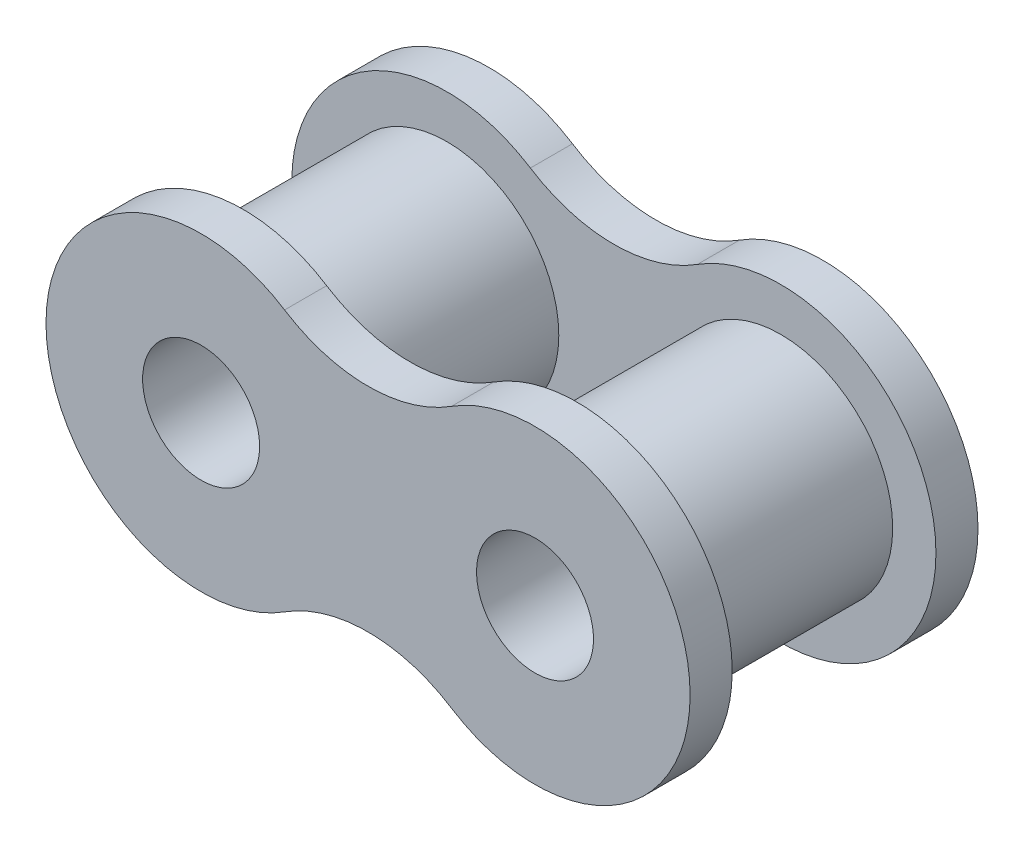
SolidWorks part; units mm, degrees
material "AISI 1020"
ref_plane "Спереди" through (0, 0, 0) normal (0, 0, 1) x (1, 0, 0)
ref_plane "Сверху" through (0, 0, 0) normal (0, 1, 0) x (1, 0, 0)
ref_plane "Справа" through (0, 0, 0) normal (1, 0, 0) x (0, 0, -1)
sketch "Эскиз1" plane through (0, 0, 0) normal (0, 0, 1) x (1, 0, 0)
  line L0 (-1000, 0) -> (49000, 0) construction
  line L1 (0, -1000) -> (0, 49000) construction
  line L2 (0, 4.0457) -> (0, -4.0457)
  circle A0 centre (-6.35, 0) radius 2.225
  arc A1 (-3.175, 4.9729) -> (-3.175, -4.9729) centre (-6.35, 0) ccw
  arc A2 (-3.175, 4.9729) -> (0, 4.0457) centre (0, 9.9457) ccw
  circle A3 centre (-6.35, 0) radius 4.255
  arc A4 (-3.175, -4.9729) -> (0, -4.0457) centre (0, -9.9457) cw
  dimension "_h2_" = 11.8
  dimension "_d2_" = 4.45
  dimension "_d1_" = 8.51
  dimension "_P" = 12.7
sketch "Эскиз2" plane through (0, 0, 0) normal (0, 1, 0) x (1, 0, 0)
  line L0 (-1000, 0) -> (49000, 0) construction
  line L2 (0, 0) -> (0, 3.875) construction
  line L3 (0, 3.875) -> (0, 5.475)
  line L4 (0, 5.475) -> (0, 7.075) construction
  line L5 (0, 7.075) -> (0, 8.425) construction
  point P7 (0, 0)
  point P9 (0, 0)
  dimension "_T" = 1.6
  dimension "_b1_" = 7.75
  dimension "_L" = 16.85
extrude "Бобышка-Вытянуть1" add sketch "Эскиз1" against normal up to vertex (5.475 mm away) from vertex contours A2 L2 A4 A1 | A0 up to point (0, 0, -5.475) starting at point (0, 0, -3.875)
extrude "Бобышка-Вытянуть2" add sketch "Эскиз1<3>" against normal up to surface (3.875 mm away) contours A3 | A0 up to face at (-4.125, 0, -3.875)
sketch "Эскиз1<3>" plane through (0, 0, 0) normal (0, 0, 1) x (1, 0, 0) same geometry as "Эскиз1"
mirror "Зеркальное отражение1" about plane through (0, 0, 0) normal (1, 0, 0) of bodies 104
mirror "Зеркальное отражение2" about plane through (0, 0, 0) normal (0, 0, 1) of bodies 105
